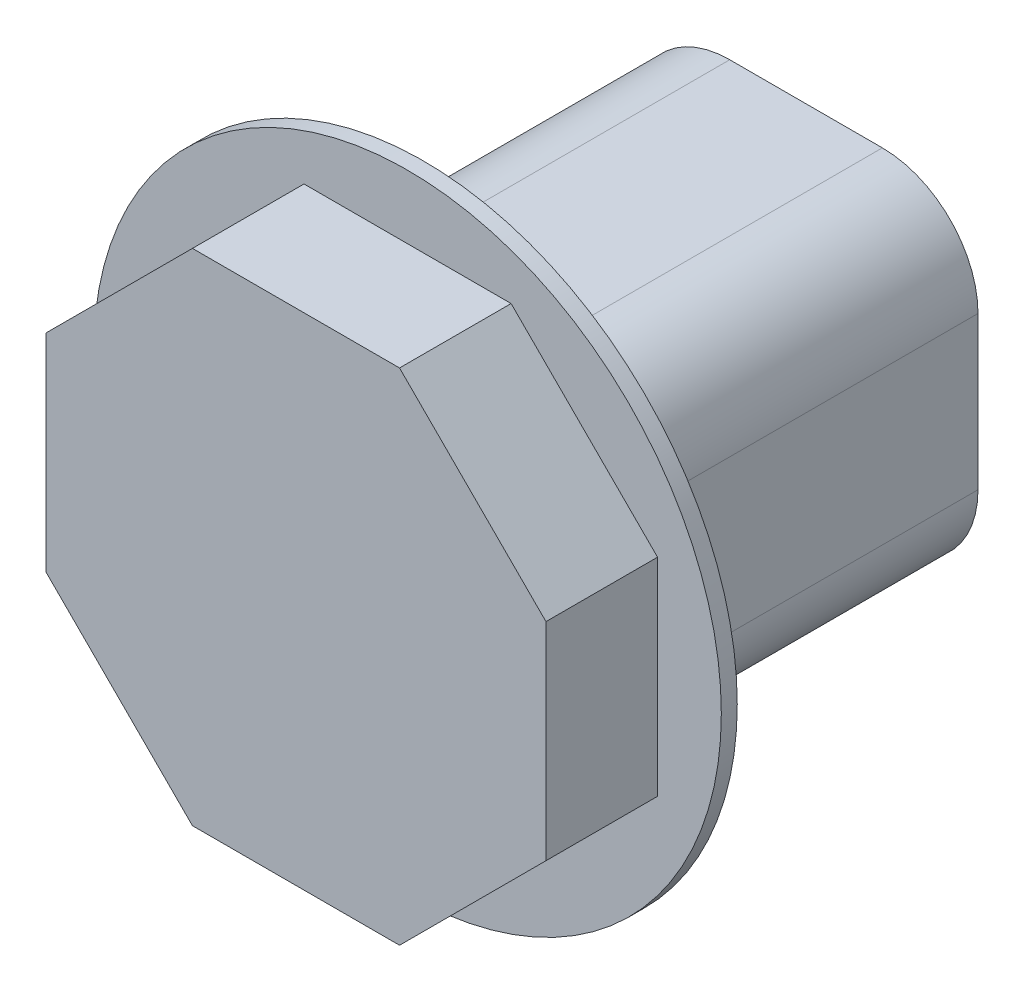
SolidWorks part; units mm, degrees
ref_plane "Front Plane" through (0, 0, 0) normal (0, 0, 1) x (1, 0, 0)
ref_plane "Top Plane" through (0, 0, 0) normal (0, 1, 0) x (1, 0, 0)
ref_plane "Right Plane" through (0, 0, 0) normal (1, 0, 0) x (0, 0, -1)
sketch "Sketch1" plane through (0, 0, 0) normal (0, 0, 1) x (1, 0, 0)
  line L1 (165.0056, 398.3587) -> (-165.0056, 398.3587)
  line L2 (-165.0056, 398.3587) -> (-398.3587, 165.0056)
  line L3 (-398.3587, 165.0056) -> (-398.3587, -165.0056)
  line L4 (-398.3587, -165.0056) -> (-165.0056, -398.3587)
  line L5 (-165.0056, -398.3587) -> (165.0056, -398.3587)
  line L6 (165.0056, -398.3587) -> (398.3587, -165.0056)
  line L7 (398.3587, -165.0056) -> (398.3587, 165.0056)
  line L8 (398.3587, 165.0056) -> (165.0056, 398.3587)
  circle A0 centre (0, 0) radius 398.3587 construction
  circle A1 centre (0, 0) radius 500
  point P12 (398.3587, 165.0056)
  dimension "D1" = 1000
extrude "Boss-Extrude1" add sketch "Sketch1" along normal blind 203.2 contours L7 L8 L1 L2 L3 L4 L5 L6 region at (0, 0, 0)
extrude "Boss-Extrude2" add sketch "Sketch1<3>" along normal blind 25.4
sketch "Sketch1<3>" plane through (0, 0, 0) normal (0, 0, 1) x (1, 0, 0) same geometry as "Sketch1"
sketch "Sketch2" plane through (0, 0, 0) normal (0, 0, -1) x (-1, 0, 0)
  line L1 (274.0041, -274.0041) -> (-274.0041, -274.0041)
  line L2 (274.0041, -274.0041) -> (274.0041, 274.0041)
  line L3 (274.0041, 274.0041) -> (-274.0041, 274.0041)
  line L4 (-274.0041, -274.0041) -> (-274.0041, 274.0041)
  line L5 (274.0041, -274.0041) -> (-274.0041, 274.0041) construction
  line L6 (274.0041, 274.0041) -> (-274.0041, -274.0041) construction
  point P0 (0, 0)
  point P6 (-274.0041, 274.0041)
extrude "Boss-Extrude3" add sketch "Sketch2" along normal blind 609.6 separate body
fillet "Fillet1" radius 152.4 4 edges at (274.0041, 274.0041, -304.8) (-274.0041, 274.0041, -304.8) (-274.0041, -274.0041, -304.8) (274.0041, -274.0041, -304.8)
